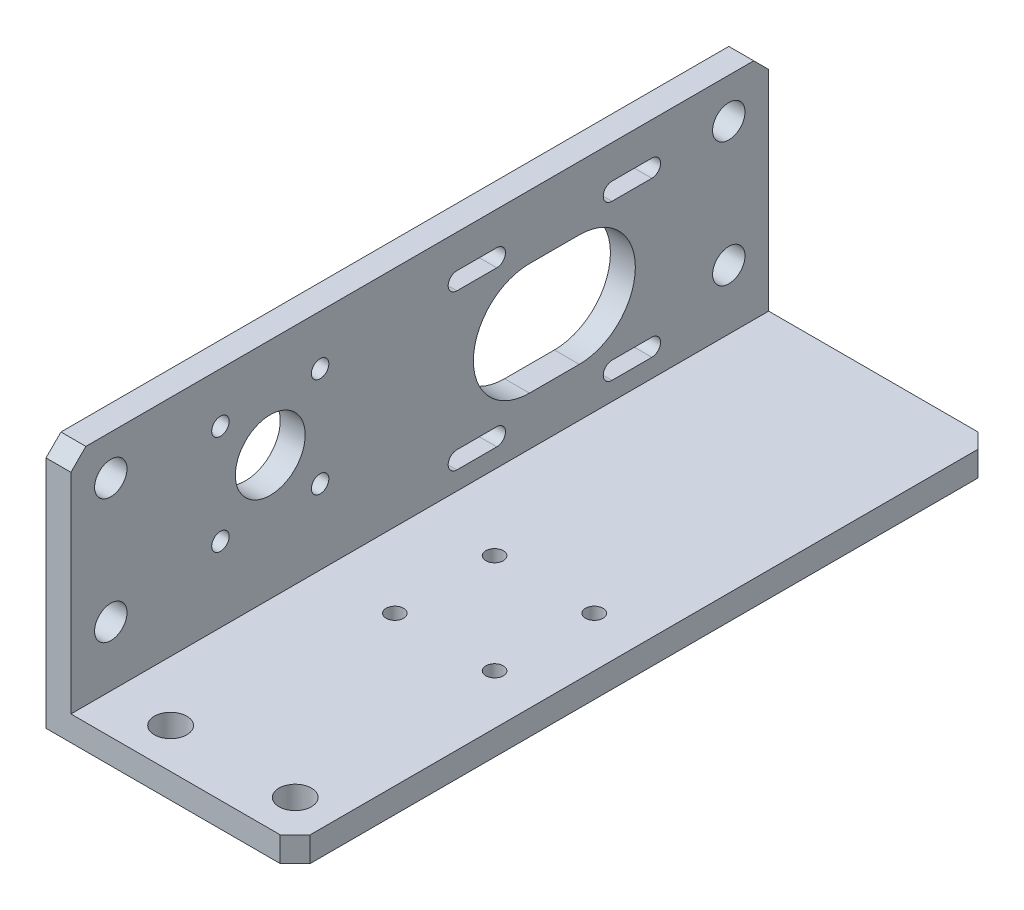
SolidWorks part; units mm, degrees
material "Lega 1060"
ref_plane "Piano frontale" through (0, 0, 0) normal (0, 0, 1) x (1, 0, 0)
ref_plane "Piano superiore" through (0, 0, 0) normal (0, 1, 0) x (1, 0, 0)
ref_plane "Piano destro" through (0, 0, 0) normal (1, 0, 0) x (0, 0, -1)
sketch "Schizzo1" plane through (0, 0, 0) normal (0, 0, 1) x (1, 0, 0)
  line L0 (0, 0) -> (0, 50)
  line L1 (0, 50) -> (5, 50)
  line L2 (5, 50) -> (5, 5)
  line L3 (5, 5) -> (50, 5)
  line L4 (50, 5) -> (50, 0)
  line L5 (50, 0) -> (0, 0)
  dimension "D1" = 5
  dimension "D2" = 5
  dimension "D3" = 50
  dimension "D4" = 50
extrude "Estrusione-Estrusione1" add sketch "Schizzo1" along normal blind 140
sketch "Schizzo2" plane through (0, 0, 0) normal (0, -1, 0) x (1, 0, 0)
  line L0 (5.4524, 132) -> (42.7933, 132) construction
  line L1 (0, 140) -> (50, 140) construction
  line L5 (50, 140) -> (50, 0) construction
  point P4 (17, 132)
  point P5 (42, 132)
  dimension "D1" = 8
  dimension "D2" = 25
  dimension "D3" = 8
sketch "Schizzo3" plane through (0, 0, 0) normal (-1, 0, 0) x (0, 0, 1)
  line L0 (132, 44.621) -> (132, 5.772) construction
  line L1 (140, 50) -> (140, 0) construction
  line L2 (140, 50) -> (0, 50) construction
  point P4 (132, 42)
  point P5 (132, 17)
  dimension "D1" = 8
  dimension "D2" = 8
  dimension "D3" = 25
hole_wizard "Foro Ø6.5 (6.5)-1" positions "Schizzo5" profile "Schizzo4" hole size "Ø6.5" standard "ISO" end condition through all
sketch "Schizzo5" plane through (0, 0, 0) normal (0, -1, 0) x (-1, 0, 0)
  point P0 (-17, -132)
  point P3 (-42, -132)
sketch "Schizzo4" plane through (17, 0, 132) normal (1, 0, 0) x (0, 0, -1)
  line L0 (0, 0) -> (0, 50)
  line L1 (0, 50) -> (3.25, 50)
  line L2 (3.25, 50) -> (3.25, 0)
  line L5 (3.25, 0) -> (0, 0)
  line L11 (0, -6.35) -> (0, 107.95) construction
  dimension "Thru Hole Dia." = 6.5
  dimension "Thru Hole Depth" = 50
hole_wizard "Foro Ø6.5 (6.5)-2" positions "Schizzo7" profile "Schizzo6" hole size "Ø6.5" standard "ISO"
sketch "Schizzo7" plane through (0, 0, 0) normal (-1, 0, 0) x (0, 0, 1)
  point P1 (132, 42)
  point P4 (132, 17)
sketch "Schizzo6" plane through (0, 42, 132) normal (0, 1, 0) x (0, 0, 1)
  line L0 (0, 0) -> (0, 6.9528)
  line L1 (0, 6.9528) -> (3.25, 5)
  line L2 (3.25, 5) -> (3.25, 0)
  line L5 (3.25, 0) -> (0, 0)
  line L10 (0, 6.9528) -> (-3.25, 5) construction
  line L11 (0, -6.35) -> (0, 107.95) construction
  dimension "Hole Dia." = 6.5
  dimension "Hole Depth" = 5
  dimension "Drill Angle" = 118
ref_plane "Piano1" through (0, 0, 70) normal (0, 0, 1) x (1, 0, 0)
mirror "Specchia1" about plane through (0, 0, 70) normal (0, 0, 1) of "Foro Ø6.5 (6.5)-2"
sketch "Schizzo8" plane through (0, 0, 0) normal (0, -1, 0) x (1, 0, 0)
  line L0 (30, 80) -> (7.0316, 80) construction
  line L1 (30, 80) -> (-7.1051, 42.8949) construction
  line L2 (0, 140) -> (50, 140) construction
  line L3 (50, 140) -> (50, 0) construction
  circle A0 centre (20, 70) radius 1.75
  circle A1 centre (20, 90) radius 1.75
  circle A2 centre (40, 90) radius 1.75
  circle A3 centre (40, 70) radius 1.75
  point P18 (30, 80)
  dimension "D3" = 3.5
  dimension "D1" = 60
  dimension "D2" = 20
  dimension "D4" = 45
  dimension "D5" = 20
  dimension "D6" = 4
extrude "Taglio-Estrusione1" cut sketch "Schizzo8" against normal up to next
sketch "Schizzo9" plane through (0, 0, 0) normal (-1, 0, 0) x (0, 0, 1)
  line L0 (100, 44.574) -> (100, 30) construction
  line L1 (100, 30) -> (63.014, 66.986) construction
  line L2 (140, 50) -> (0, 50) construction
  line L3 (140, 50) -> (140, 0) construction
  circle A0 centre (90, 40) radius 1.75
  circle A1 centre (110, 40) radius 1.75
  circle A2 centre (110, 20) radius 1.75
  circle A3 centre (90, 20) radius 1.75
  circle A4 centre (100, 30) radius 7
  point P18 (100, 30)
  dimension "D4" = 3.5
  dimension "D7" = 14
  dimension "D1" = 20
  dimension "D2" = 40
  dimension "D3" = 45
  dimension "D5" = 20
  dimension "D6" = 4
extrude "Taglio-Estrusione2" cut sketch "Schizzo9" against normal up to next
sketch "Schizzo11" plane through (0, 0, 0) normal (-1, 0, 0) x (0, 0, 1)
  line L0 (32.6037, 26) -> (56.4009, 26) construction
  line L1 (62.5563, 10.4437) -> (54.5563, 10.4437) construction
  line L2 (140, 0) -> (0, 0) construction
  line L3 (62.5563, 41.5563) -> (54.5563, 41.5563) construction
  line L4 (62.5563, 39.8063) -> (54.5563, 39.8063)
  line L5 (62.5563, 43.3063) -> (54.5563, 43.3063)
  line L6 (43, 26) -> (43, 48.418) construction
  line L7 (62.5563, 12.1937) -> (54.5563, 12.1937)
  line L8 (62.5563, 8.6937) -> (54.5563, 8.6937)
  line L9 (23.4437, 10.4437) -> (31.4437, 10.4437) construction
  line L10 (23.4437, 12.1937) -> (31.4437, 12.1937)
  line L11 (23.4437, 8.6937) -> (31.4437, 8.6937)
  line L12 (23.4437, 41.5563) -> (31.4437, 41.5563) construction
  line L13 (23.4437, 39.8063) -> (31.4437, 39.8063)
  line L14 (23.4437, 43.3063) -> (31.4437, 43.3063)
  line L15 (48, 26) -> (38, 26) construction
  line L16 (48, 14.75) -> (38, 14.75)
  line L17 (48, 37.25) -> (38, 37.25)
  arc A1 (62.5563, 39.8063) -> (62.5563, 43.3063) centre (62.5563, 41.5563) ccw
  arc A2 (62.5563, 12.1937) -> (62.5563, 8.6937) centre (62.5563, 10.4437) cw
  arc A3 (54.5563, 8.6937) -> (54.5563, 12.1937) centre (54.5563, 10.4437) cw
  arc A4 (23.4437, 12.1937) -> (23.4437, 8.6937) centre (23.4437, 10.4437) ccw
  arc A5 (31.4437, 8.6937) -> (31.4437, 12.1937) centre (31.4437, 10.4437) ccw
  arc A7 (54.5563, 43.3063) -> (54.5563, 39.8063) centre (54.5563, 41.5563) ccw
  arc A8 (23.4437, 39.8063) -> (23.4437, 43.3063) centre (23.4437, 41.5563) cw
  arc A9 (31.4437, 43.3063) -> (31.4437, 39.8063) centre (31.4437, 41.5563) cw
  arc A10 (48, 14.75) -> (48, 37.25) centre (48, 26) ccw
  arc A11 (38, 37.25) -> (38, 14.75) centre (38, 26) ccw
  point P10 (58.5563, 10.4437)
  point P13 (58.5563, 41.5563)
  point P18 (27.4437, 10.4437)
  point P20 (43, 26)
  point P33 (27.4437, 41.5563)
  point P40 (43, 26)
  dimension "D5" = 10
  dimension "D1" = 22.5
  dimension "D4" = 26
  dimension "D8" = 3.5
  dimension "D9" = 8
extrude "Taglio-Estrusione4" cut sketch "Schizzo11" against normal up to next
chamfer "Smusso1" distance 3 angle 45 4 edges at (50, 2.5, 0) (2.5, 50, 0) (2.5, 50, 140) (50, 2.5, 140)
